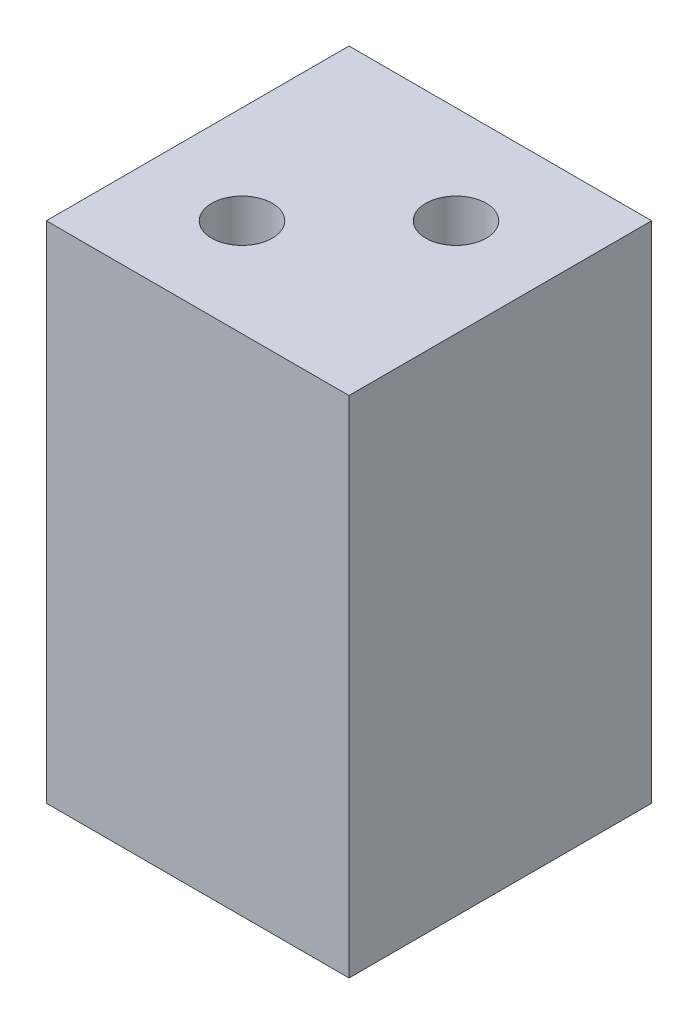
SolidWorks part; units mm, degrees
ref_plane "Front Plane" through (0, 0, 0) normal (0, 0, 1) x (1, 0, 0)
ref_plane "Top Plane" through (0, 0, 0) normal (0, 1, 0) x (1, 0, 0)
ref_plane "Right Plane" through (0, 0, 0) normal (1, 0, 0) x (0, 0, -1)
sketch "Sketch1" plane through (0, 0, 0) normal (0, 1, 0) x (1, 0, 0)
  line L0 (-15, -15) -> (15, 15) construction
  line L1 (-15, 15) -> (15, 15)
  line L2 (-15, 15) -> (-15, -15)
  line L3 (-15, -15) -> (15, -15)
  line L4 (15, 15) -> (15, -15)
  circle A0 centre (-5.3033, -5.3033) radius 3
  circle A1 centre (5.3033, 5.3033) radius 3
  point P4 (0, 0)
  dimension "D3" = 6
  dimension "D4" = 6
  dimension "D1" = 30
  dimension "D2" = 30
  dimension "D5" = 15
  dimension "D6" = 7.5
extrude "Boss-Extrude1" add sketch "Sketch1" along normal blind 50
